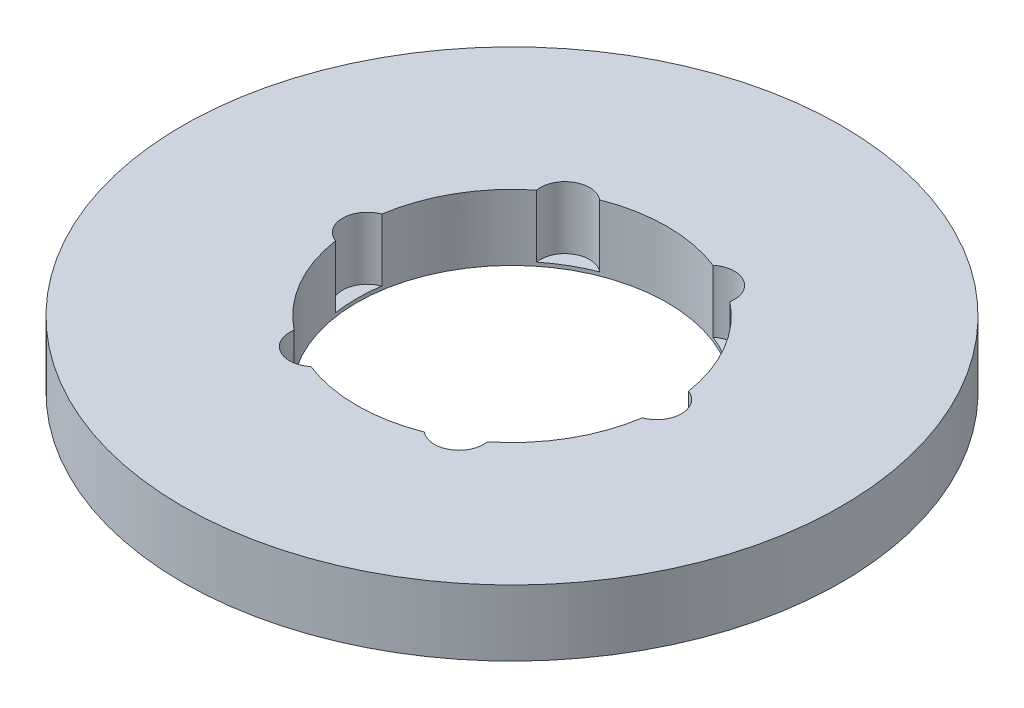
SolidWorks part; units mm, degrees
ref_plane "Front Plane" through (0, 0, 0) normal (0, 0, 1) x (1, 0, 0)
ref_plane "Top Plane" through (0, 0, 0) normal (0, 1, 0) x (1, 0, 0)
ref_plane "Right Plane" through (0, 0, 0) normal (1, 0, 0) x (0, 0, -1)
sketch "Sketch1" plane through (0, 0, 0) normal (0, 1, 0) x (1, 0, 0)
  circle A0 centre (0, 0) radius 85
  dimension "FLANGE_OD" = 170
extrude "Boss-Extrude1" add sketch "Sketch1" along normal blind 17
sketch "Sketch2" plane through (0, 0, 0) normal (0, 1, 0) x (1, 0, 0)
  circle A0 centre (0, 0) radius 40
  dimension "BORE_D" = 80
extrude "Cut-Extrude1" cut sketch "Sketch2" along normal through all
sketch "Sketch3" plane through (0, 17, 0) normal (0, 1, 0) x (1, 0, 0)
  circle A0 centre (0, 0) radius 37.3487 construction
  circle A1 centre (-37.3487, 0) radius 6.3546
  dimension "BOLT_D" = 12.7093
  dimension "BOLT_PCD" = 74.6973
extrude "Cut-Extrude2" cut sketch "Sketch3" against normal blind 16.0804
pattern_circular "CirPattern1" count 6 over 360 about axis through (0, 0, 0) along (0, 1, 0) of "Cut-Extrude2"
